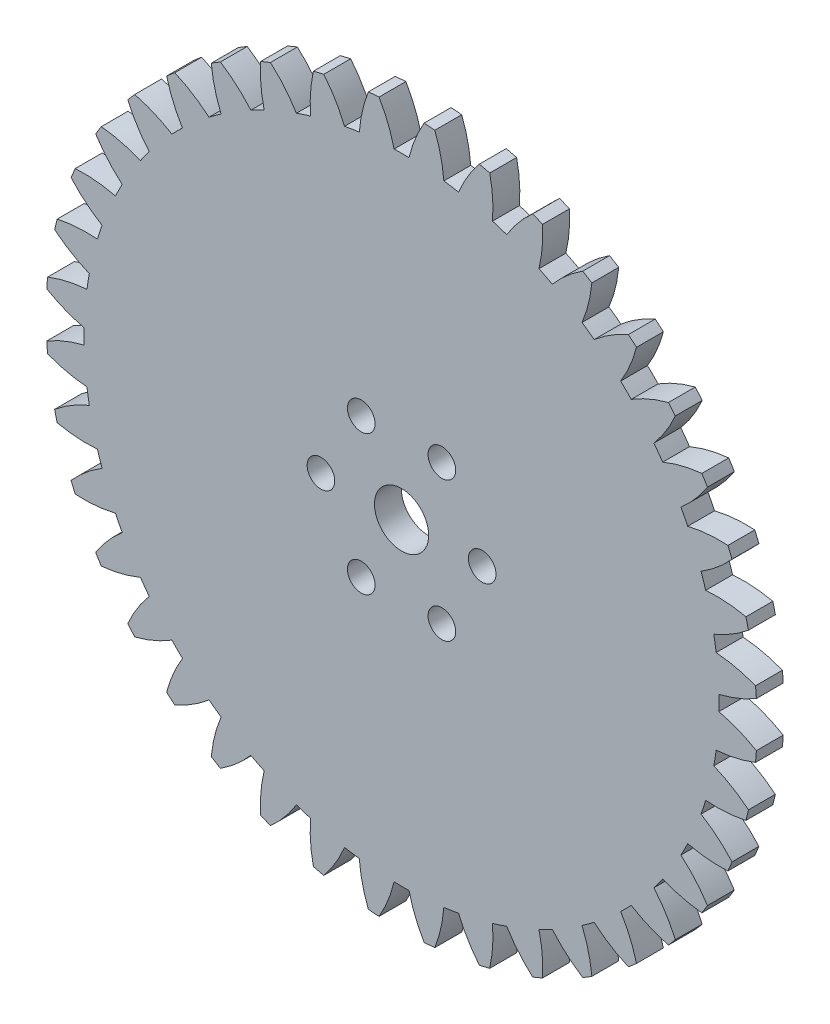
SolidWorks part; units mm, degrees
ref_plane "Front Plane" through (0, 0, 0) normal (0, 0, 1) x (1, 0, 0)
ref_plane "Top Plane" through (0, 0, 0) normal (0, 1, 0) x (1, 0, 0)
ref_plane "Right Plane" through (0, 0, 0) normal (1, 0, 0) x (0, 0, -1)
ref_axis "Axis1" through (0, -55, 0) along (0, 1, 0)
sketch "Model" plane through (0, 0, 0) normal (0, 0, 1) x (1, 0, 0)
  circle A0 centre (4.7625, 8.2489) radius 1.632
  circle A1 centre (-4.7625, 8.2489) radius 1.632
  circle A2 centre (-9.525, 0) radius 1.632
  circle A3 centre (-4.7625, -8.2489) radius 1.632
  circle A4 centre (4.7625, -8.2489) radius 1.632
  circle A5 centre (9.525, 0) radius 1.632
  arc A6 (-41.9154, 2.664) -> (-37.4886, 0.8828) centre (-33.7965, 16.451) ccw
  arc A7 (-37.4886, 0.8828) -> (-37.4886, -0.8828) centre (0, 0) ccw
  arc A8 (-37.4886, -0.8828) -> (-41.9154, -2.664) centre (-33.7965, -16.451) ccw
  arc A9 (-41.9154, -2.664) -> (-41.8161, -3.9259) centre (0, 0) ccw
  arc A10 (-41.8161, -3.9259) -> (-37.1652, -4.9926) centre (-35.9539, 10.9615) ccw
  arc A11 (-37.1652, -4.9926) -> (-36.889, -6.7365) centre (0, 0) ccw
  arc A12 (-36.889, -6.7365) -> (-40.9826, -9.1882) centre (-30.8069, -21.5354) ccw
  arc A13 (-40.9826, -9.1882) -> (-40.6872, -10.419) centre (0, 0) ccw
  arc A14 (-40.6872, -10.419) -> (-35.9266, -10.745) centre (-37.226, 5.2021) ccw
  arc A15 (-35.9266, -10.745) -> (-35.381, -12.4242) centre (0, 0) ccw
  arc A16 (-35.381, -12.4242) -> (-39.0407, -15.4862) centre (-27.0587, -26.0895) ccw
  arc A17 (-39.0407, -15.4862) -> (-38.5563, -16.6556) centre (0, 0) ccw
  arc A18 (-38.5563, -16.6556) -> (-33.8034, -16.2329) centre (-37.5815, -0.6853) ccw
  arc A19 (-33.8034, -16.2329) -> (-33.0018, -17.8061) centre (0, 0) ccw
  arc A20 (-33.0018, -17.8061) -> (-36.1375, -21.4028) centre (-22.6443, -30.0012) ccw
  arc A21 (-36.1375, -21.4028) -> (-35.4761, -22.4821) centre (0, 0) ccw
  arc A22 (-35.4761, -22.4821) -> (-30.8478, -21.321) centre (-37.0116, -6.5559) ccw
  arc A23 (-30.8478, -21.321) -> (-29.81, -22.7495) centre (0, 0) ccw
  arc A24 (-29.81, -22.7495) -> (-32.3445, -26.7925) centre (-17.6723, -33.1742) ccw
  arc A25 (-32.3445, -26.7925) -> (-31.5224, -27.755) centre (0, 0) ccw
  arc A26 (-31.5224, -27.755) -> (-27.1327, -25.8842) centre (-35.5303, -12.2651) ccw
  arc A27 (-27.1327, -25.8842) -> (-25.8842, -27.1327) centre (0, 0) ccw
  arc A28 (-25.8842, -27.1327) -> (-27.755, -31.5224) centre (-12.2651, -35.5303) ccw
  arc A29 (-27.755, -31.5224) -> (-26.7925, -32.3445) centre (0, 0) ccw
  arc A30 (-26.7925, -32.3445) -> (-22.7495, -29.81) centre (-33.1742, -17.6723) ccw
  arc A31 (-22.7495, -29.81) -> (-21.321, -30.8478) centre (0, 0) ccw
  arc A32 (-21.321, -30.8478) -> (-22.4821, -35.4761) centre (-6.5559, -37.0116) ccw
  arc A33 (-22.4821, -35.4761) -> (-21.4028, -36.1375) centre (0, 0) ccw
  arc A34 (-21.4028, -36.1375) -> (-17.8061, -33.0018) centre (-30.0012, -22.6443) ccw
  arc A35 (-17.8061, -33.0018) -> (-16.2329, -33.8034) centre (0, 0) ccw
  arc A36 (-16.2329, -33.8034) -> (-16.6556, -38.5563) centre (-0.6853, -37.5815) ccw
  arc A37 (-16.6556, -38.5563) -> (-15.4862, -39.0407) centre (0, 0) ccw
  arc A38 (-15.4862, -39.0407) -> (-12.4242, -35.381) centre (-26.0895, -27.0587) ccw
  arc A39 (-12.4242, -35.381) -> (-10.745, -35.9266) centre (0, 0) ccw
  arc A40 (-10.745, -35.9266) -> (-10.419, -40.6872) centre (5.2021, -37.226) ccw
  arc A41 (-10.419, -40.6872) -> (-9.1882, -40.9826) centre (0, 0) ccw
  arc A42 (-9.1882, -40.9826) -> (-6.7365, -36.889) centre (-21.5354, -30.8069) ccw
  arc A43 (-6.7365, -36.889) -> (-4.9926, -37.1652) centre (0, 0) ccw
  arc A44 (-4.9926, -37.1652) -> (-3.9259, -41.8161) centre (10.9615, -35.9539) ccw
  arc A45 (-3.9259, -41.8161) -> (-2.664, -41.9154) centre (0, 0) ccw
  arc A46 (-2.664, -41.9154) -> (-0.8828, -37.4886) centre (-16.451, -33.7965) ccw
  arc A47 (-0.8828, -37.4886) -> (0.8828, -37.4886) centre (0, 0) ccw
  arc A48 (0.8828, -37.4886) -> (2.664, -41.9154) centre (16.451, -33.7965) ccw
  arc A49 (2.664, -41.9154) -> (3.9259, -41.8161) centre (0, 0) ccw
  arc A50 (3.9259, -41.8161) -> (4.9926, -37.1652) centre (-10.9615, -35.9539) ccw
  arc A51 (4.9926, -37.1652) -> (6.7365, -36.889) centre (0, 0) ccw
  arc A52 (6.7365, -36.889) -> (9.1882, -40.9826) centre (21.5354, -30.8069) ccw
  arc A53 (9.1882, -40.9826) -> (10.419, -40.6872) centre (0, 0) ccw
  arc A54 (10.419, -40.6872) -> (10.745, -35.9266) centre (-5.2021, -37.226) ccw
  arc A55 (10.745, -35.9266) -> (12.4242, -35.381) centre (0, 0) ccw
  arc A56 (12.4242, -35.381) -> (15.4862, -39.0407) centre (26.0895, -27.0587) ccw
  arc A57 (15.4862, -39.0407) -> (16.6556, -38.5563) centre (0, 0) ccw
  arc A58 (16.6556, -38.5563) -> (16.2329, -33.8034) centre (0.6853, -37.5815) ccw
  arc A59 (16.2329, -33.8034) -> (17.8061, -33.0018) centre (0, 0) ccw
  arc A60 (17.8061, -33.0018) -> (21.4028, -36.1375) centre (30.0012, -22.6443) ccw
  arc A61 (21.4028, -36.1375) -> (22.4821, -35.4761) centre (0, 0) ccw
  arc A62 (22.4821, -35.4761) -> (21.321, -30.8478) centre (6.5559, -37.0116) ccw
  arc A63 (21.321, -30.8478) -> (22.7495, -29.81) centre (0, 0) ccw
  arc A64 (22.7495, -29.81) -> (26.7925, -32.3445) centre (33.1742, -17.6723) ccw
  arc A65 (26.7925, -32.3445) -> (27.755, -31.5224) centre (0, 0) ccw
  arc A66 (27.755, -31.5224) -> (25.8842, -27.1327) centre (12.2651, -35.5303) ccw
  arc A67 (25.8842, -27.1327) -> (27.1327, -25.8842) centre (0, 0) ccw
  arc A68 (27.1327, -25.8842) -> (31.5224, -27.755) centre (35.5303, -12.2651) ccw
  arc A69 (31.5224, -27.755) -> (32.3445, -26.7925) centre (0, 0) ccw
  arc A70 (32.3445, -26.7925) -> (29.81, -22.7495) centre (17.6723, -33.1742) ccw
  arc A71 (29.81, -22.7495) -> (30.8478, -21.321) centre (0, 0) ccw
  arc A72 (30.8478, -21.321) -> (35.4761, -22.4821) centre (37.0116, -6.5559) ccw
  arc A73 (35.4761, -22.4821) -> (36.1375, -21.4028) centre (0, 0) ccw
  arc A74 (36.1375, -21.4028) -> (33.0018, -17.8061) centre (22.6443, -30.0012) ccw
  arc A75 (33.0018, -17.8061) -> (33.8034, -16.2329) centre (0, 0) ccw
  arc A76 (33.8034, -16.2329) -> (38.5563, -16.6556) centre (37.5815, -0.6853) ccw
  arc A77 (38.5563, -16.6556) -> (39.0407, -15.4862) centre (0, 0) ccw
  arc A78 (39.0407, -15.4862) -> (35.381, -12.4242) centre (27.0587, -26.0895) ccw
  arc A79 (35.381, -12.4242) -> (35.9266, -10.745) centre (0, 0) ccw
  arc A80 (35.9266, -10.745) -> (40.6872, -10.419) centre (37.226, 5.2021) ccw
  arc A81 (40.6872, -10.419) -> (40.9826, -9.1882) centre (0, 0) ccw
  arc A82 (40.9826, -9.1882) -> (36.889, -6.7365) centre (30.8069, -21.5354) ccw
  arc A83 (36.889, -6.7365) -> (37.1652, -4.9926) centre (0, 0) ccw
  arc A84 (37.1652, -4.9926) -> (41.8161, -3.9259) centre (35.9539, 10.9615) ccw
  arc A85 (41.8161, -3.9259) -> (41.9154, -2.664) centre (0, 0) ccw
  arc A86 (41.9154, -2.664) -> (37.4886, -0.8828) centre (33.7965, -16.451) ccw
  arc A87 (37.4886, -0.8828) -> (37.4886, 0.8828) centre (0, 0) ccw
  arc A88 (37.4886, 0.8828) -> (41.9154, 2.664) centre (33.7965, 16.451) ccw
  arc A89 (41.9154, 2.664) -> (41.8161, 3.9259) centre (0, 0) ccw
  arc A90 (41.8161, 3.9259) -> (37.1652, 4.9926) centre (35.9539, -10.9615) ccw
  arc A91 (37.1652, 4.9926) -> (36.889, 6.7365) centre (0, 0) ccw
  arc A92 (36.889, 6.7365) -> (40.9826, 9.1882) centre (30.8069, 21.5354) ccw
  arc A93 (40.9826, 9.1882) -> (40.6872, 10.419) centre (0, 0) ccw
  arc A94 (40.6872, 10.419) -> (35.9266, 10.745) centre (37.226, -5.2021) ccw
  arc A95 (35.9266, 10.745) -> (35.381, 12.4242) centre (0, 0) ccw
  arc A96 (35.381, 12.4242) -> (39.0407, 15.4862) centre (27.0587, 26.0895) ccw
  arc A97 (39.0407, 15.4862) -> (38.5563, 16.6556) centre (0, 0) ccw
  arc A98 (38.5563, 16.6556) -> (33.8034, 16.2329) centre (37.5815, 0.6853) ccw
  arc A99 (33.8034, 16.2329) -> (33.0018, 17.8061) centre (0, 0) ccw
  arc A100 (33.0018, 17.8061) -> (36.1375, 21.4028) centre (22.6443, 30.0012) ccw
  arc A101 (36.1375, 21.4028) -> (35.4761, 22.4821) centre (0, 0) ccw
  arc A102 (35.4761, 22.4821) -> (30.8478, 21.321) centre (37.0116, 6.5559) ccw
  arc A103 (30.8478, 21.321) -> (29.81, 22.7495) centre (0, 0) ccw
  arc A104 (29.81, 22.7495) -> (32.3445, 26.7925) centre (17.6723, 33.1742) ccw
  arc A105 (32.3445, 26.7925) -> (31.5224, 27.755) centre (0, 0) ccw
  arc A106 (31.5224, 27.755) -> (27.1327, 25.8842) centre (35.5303, 12.2651) ccw
  arc A107 (27.1327, 25.8842) -> (25.8842, 27.1327) centre (0, 0) ccw
  arc A108 (25.8842, 27.1327) -> (27.755, 31.5224) centre (12.2651, 35.5303) ccw
  arc A109 (27.755, 31.5224) -> (26.7925, 32.3445) centre (0, 0) ccw
  arc A110 (26.7925, 32.3445) -> (22.7495, 29.81) centre (33.1742, 17.6723) ccw
  arc A111 (22.7495, 29.81) -> (21.321, 30.8478) centre (0, 0) ccw
  arc A112 (21.321, 30.8478) -> (22.4821, 35.4761) centre (6.5559, 37.0116) ccw
  arc A113 (22.4821, 35.4761) -> (21.4028, 36.1375) centre (0, 0) ccw
  arc A114 (21.4028, 36.1375) -> (17.8061, 33.0018) centre (30.0012, 22.6443) ccw
  arc A115 (17.8061, 33.0018) -> (16.2329, 33.8034) centre (0, 0) ccw
  arc A116 (16.2329, 33.8034) -> (16.6556, 38.5563) centre (0.6853, 37.5815) ccw
  arc A117 (16.6556, 38.5563) -> (15.4862, 39.0407) centre (0, 0) ccw
  arc A118 (15.4862, 39.0407) -> (12.4242, 35.381) centre (26.0895, 27.0587) ccw
  arc A119 (12.4242, 35.381) -> (10.745, 35.9266) centre (0, 0) ccw
  arc A120 (10.745, 35.9266) -> (10.419, 40.6872) centre (-5.2021, 37.226) ccw
  arc A121 (10.419, 40.6872) -> (9.1882, 40.9826) centre (0, 0) ccw
  arc A122 (9.1882, 40.9826) -> (6.7365, 36.889) centre (21.5354, 30.8069) ccw
  arc A123 (6.7365, 36.889) -> (4.9926, 37.1652) centre (0, 0) ccw
  arc A124 (4.9926, 37.1652) -> (3.9259, 41.8161) centre (-10.9615, 35.9539) ccw
  arc A125 (3.9259, 41.8161) -> (2.664, 41.9154) centre (0, 0) ccw
  arc A126 (2.664, 41.9154) -> (0.8828, 37.4886) centre (16.451, 33.7965) ccw
  arc A127 (0.8828, 37.4886) -> (-0.8828, 37.4886) centre (0, 0) ccw
  arc A128 (-0.8828, 37.4886) -> (-2.664, 41.9154) centre (-16.451, 33.7965) ccw
  arc A129 (-2.664, 41.9154) -> (-3.9259, 41.8161) centre (0, 0) ccw
  arc A130 (-3.9259, 41.8161) -> (-4.9926, 37.1652) centre (10.9615, 35.9539) ccw
  arc A131 (-4.9926, 37.1652) -> (-6.7365, 36.889) centre (0, 0) ccw
  arc A132 (-6.7365, 36.889) -> (-9.1882, 40.9826) centre (-21.5354, 30.8069) ccw
  arc A133 (-9.1882, 40.9826) -> (-10.419, 40.6872) centre (0, 0) ccw
  arc A134 (-10.419, 40.6872) -> (-10.745, 35.9266) centre (5.2021, 37.226) ccw
  arc A135 (-10.745, 35.9266) -> (-12.4242, 35.381) centre (0, 0) ccw
  arc A136 (-12.4242, 35.381) -> (-15.4862, 39.0407) centre (-26.0895, 27.0587) ccw
  arc A137 (-15.4862, 39.0407) -> (-16.6556, 38.5563) centre (0, 0) ccw
  arc A138 (-16.6556, 38.5563) -> (-16.2329, 33.8034) centre (-0.6853, 37.5815) ccw
  arc A139 (-16.2329, 33.8034) -> (-17.8061, 33.0018) centre (0, 0) ccw
  arc A140 (-17.8061, 33.0018) -> (-21.4028, 36.1375) centre (-30.0012, 22.6443) ccw
  arc A141 (-21.4028, 36.1375) -> (-22.4821, 35.4761) centre (0, 0) ccw
  arc A142 (-22.4821, 35.4761) -> (-21.321, 30.8478) centre (-6.5559, 37.0116) ccw
  arc A143 (-21.321, 30.8478) -> (-22.7495, 29.81) centre (0, 0) ccw
  arc A144 (-22.7495, 29.81) -> (-26.7925, 32.3445) centre (-33.1742, 17.6723) ccw
  arc A145 (-26.7925, 32.3445) -> (-27.755, 31.5224) centre (0, 0) ccw
  arc A146 (-27.755, 31.5224) -> (-25.8842, 27.1327) centre (-12.2651, 35.5303) ccw
  arc A147 (-25.8842, 27.1327) -> (-27.1327, 25.8842) centre (0, 0) ccw
  arc A148 (-27.1327, 25.8842) -> (-31.5224, 27.755) centre (-35.5303, 12.2651) ccw
  arc A149 (-31.5224, 27.755) -> (-32.3445, 26.7925) centre (0, 0) ccw
  arc A150 (-32.3445, 26.7925) -> (-29.81, 22.7495) centre (-17.6723, 33.1742) ccw
  arc A151 (-29.81, 22.7495) -> (-30.8478, 21.321) centre (0, 0) ccw
  arc A152 (-30.8478, 21.321) -> (-35.4761, 22.4821) centre (-37.0116, 6.5559) ccw
  arc A153 (-35.4761, 22.4821) -> (-36.1375, 21.4028) centre (0, 0) ccw
  arc A154 (-36.1375, 21.4028) -> (-33.0018, 17.8061) centre (-22.6443, 30.0012) ccw
  arc A155 (-33.0018, 17.8061) -> (-33.8034, 16.2329) centre (0, 0) ccw
  arc A156 (-33.8034, 16.2329) -> (-38.5563, 16.6556) centre (-37.5815, 0.6853) ccw
  arc A157 (-38.5563, 16.6556) -> (-39.0407, 15.4862) centre (0, 0) ccw
  arc A158 (-39.0407, 15.4862) -> (-35.381, 12.4242) centre (-27.0587, 26.0895) ccw
  arc A159 (-35.381, 12.4242) -> (-35.9266, 10.745) centre (0, 0) ccw
  arc A160 (-35.9266, 10.745) -> (-40.6872, 10.419) centre (-37.226, -5.2021) ccw
  arc A161 (-40.6872, 10.419) -> (-40.9826, 9.1882) centre (0, 0) ccw
  arc A162 (-40.9826, 9.1882) -> (-36.889, 6.7365) centre (-30.8069, 21.5354) ccw
  arc A163 (-36.889, 6.7365) -> (-37.1652, 4.9926) centre (0, 0) ccw
  arc A164 (-37.1652, 4.9926) -> (-41.8161, 3.9259) centre (-35.9539, -10.9615) ccw
  arc A165 (-41.8161, 3.9259) -> (-41.9154, 2.664) centre (0, 0) ccw
  circle A166 centre (0, 0) radius 3.2
extrude "Boss-Extrude1" add sketch "Model" along normal blind 3.175
